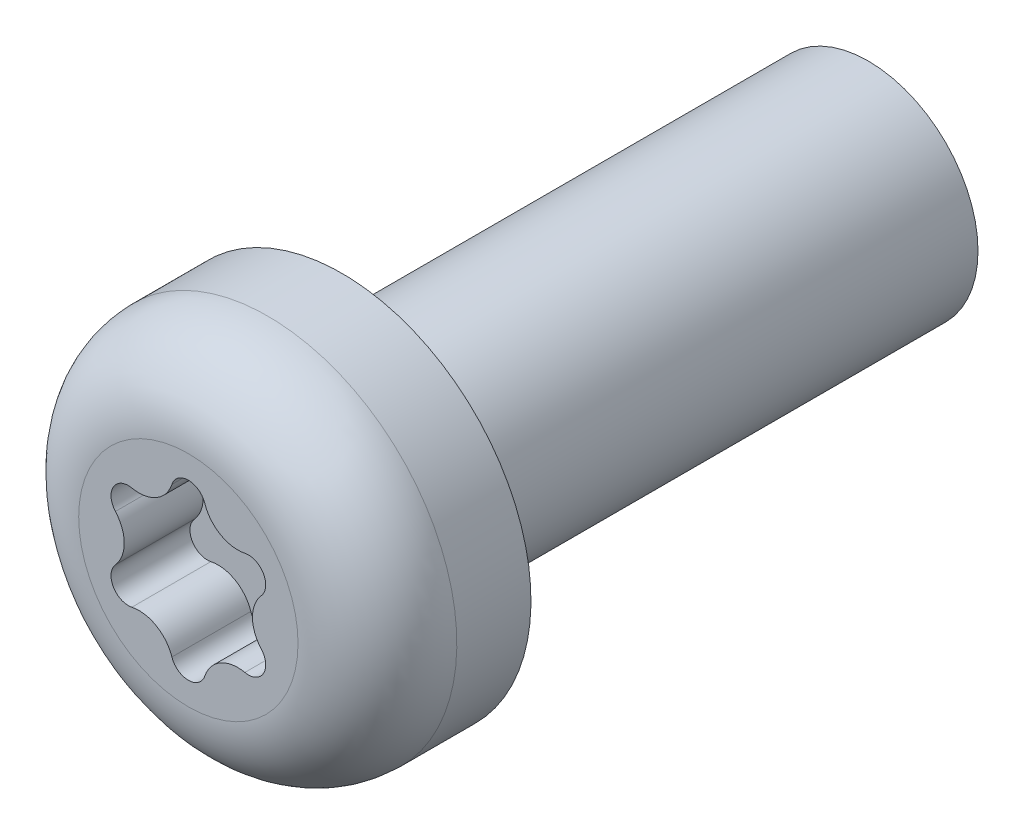
SolidWorks part; units mm, degrees
material "Alloy Steel"
ref_plane "Front Plane" through (0, 0, 0) normal (0, 0, 1) x (1, 0, 0)
ref_plane "Top Plane" through (0, 0, 0) normal (0, 1, 0) x (1, 0, 0)
ref_plane "Right Plane" through (0, 0, 0) normal (1, 0, 0) x (0, 0, -1)
ref_axis "Axis1" through (0, 0, -52.8182) along (0, 0, 1)
ref_axis "Axis2" through (0, -15.5981, 0) along (0, 1, 0)
ref_axis "Axis3" through (-12.2581, 0, 0) along (1, 0, 0)
sketch "Sketch1" plane through (0, 0, 0) normal (1, 0, 0) x (0, 0, -1)
  line L0 (-3.5, 0) -> (-3.5, 2.5)
  line L1 (-1.69, 4.31) -> (0, 4.31)
  line L2 (0, 4.31) -> (0, 2.5)
  line L3 (0, 2.5) -> (12, 2.5)
  line L4 (12, 2.5) -> (12, 0)
  line L5 (12, 0) -> (-3.5, 0)
  line L6 (-5.5849, 0) -> (13.8966, 0) construction
  arc A0 (-1.69, 4.31) -> (-3.5, 2.5) centre (-1.69, 2.5) ccw
  point P13 (0, 2.5)
  dimension "D1" = 5
  dimension "D2" = 8.62
  dimension "D3" = 3.5
  dimension "D4" = 5
  dimension "Length" = 12
revolve "Revolve1" add sketch "Sketch1" angle 360 about L6
cosmetic thread "Cosmetic Thread1" parameters "D1"=12, "D2"=2.439
sketch "Sketch2" plane through (0, 0, 3.5) normal (0, 0, 1) x (1, 0, 0)
  line L0 (0, 0) -> (0, 1.975) construction
  line L1 (-0.7308, 1.2658) -> (0, 0)
  line L2 (0, 0) -> (0.7308, 1.2658)
  arc A0 (-0.7308, 1.2658) -> (-0.3753, 1.7033) centre (-1.1258, 1.9499) ccw
  arc A1 (-0.3753, 1.7033) -> (0.3753, 1.7033) centre (0, 1.58) cw
  arc A2 (0.3753, 1.7033) -> (0.7308, 1.2658) centre (1.1258, 1.9499) ccw
  circle A3 centre (0, 0) radius 1.975 construction
  dimension "D1" = 3.95
extrude "Cut-Extrude1" cut sketch "Sketch2" against normal blind 1.8
pattern_circular "CirPattern1" count 6 over 360 about axis through (0, 0, 5.5849) along (0, 0, 1) of "Cut-Extrude1"
equation "\"D3@Sketch2\"=\"D1@Sketch2\"*.1"
equation "\"D4@Sketch2\"=\"D3@Sketch2\"*2"
